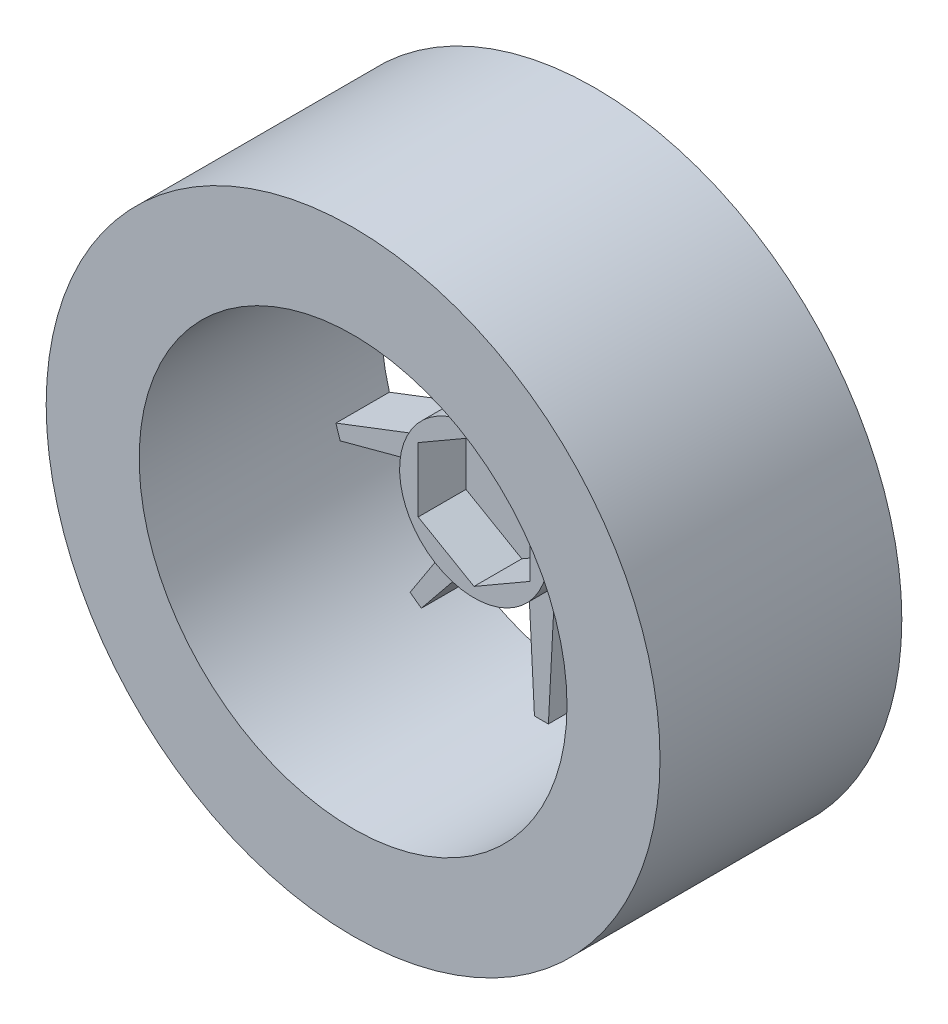
SolidWorks part; units mm, degrees
ref_plane "Front Plane" through (0, 0, 0) normal (0, 0, 1) x (1, 0, 0)
ref_plane "Top Plane" through (0, 0, 0) normal (0, 1, 0) x (1, 0, 0)
ref_plane "Right Plane" through (0, 0, 0) normal (1, 0, 0) x (0, 0, -1)
sketch "Sketch1" plane through (0, 0, 0) normal (0, 0, 1) x (1, 0, 0)
  circle A0 centre (0, 0) radius 33
  circle A1 centre (0, 0) radius 23
  dimension "D1" = 66
  dimension "D2" = 10
extrude "Boss-Extrude1" add sketch "Sketch1" along normal blind 26
sketch "Sketch3" plane through (0, 0, 0) normal (0, 0, 1) x (1, 0, 0)
  circle A0 centre (0, 0) radius 8
  circle A1 centre (0, 0) radius 1.875
  dimension "D1" = 16
  dimension "D2" = 3.75
extrude "Boss-Extrude2" add sketch "Sketch3" along normal blind 13 separate body
sketch "Sketch4" plane through (0, 0, 13) normal (0, 0, 1) x (1, 0, 0)
  line L0 (0, -14.3) -> (0, 14.3) construction
  line L1 (0, 6.9282) -> (-6, 3.4641)
  line L2 (-6, 3.4641) -> (-6, -3.4641)
  line L3 (-6, -3.4641) -> (0, -6.9282)
  line L4 (0, -6.9282) -> (6, -3.4641)
  line L5 (6, -3.4641) -> (6, 3.4641)
  line L6 (6, 3.4641) -> (0, 6.9282)
  circle A0 centre (0, 0) radius 6 construction
  point P1 (0, 6.5361)
  dimension "D1" = 12
extrude "Cut-Extrude1" cut sketch "Sketch4" against normal blind 5.14
sketch "Sketch5" plane through (0, 0, 0) normal (0, 0, 1) x (1, 0, 0)
  line L0 (-1.5, 8.5942) -> (-0.75, 22.9878)
  line L1 (0, -14.3) -> (0, 14.3) construction
  line L2 (1.5, 8.5942) -> (0.75, 22.9878)
  circle A0 centre (0, 0) radius 23 construction
  arc A1 (-1.5, 8.5942) -> (-2.221, 7.6855) centre (-2.4986, 8.6462) cw
  circle A2 centre (0, 0) radius 8 construction
  arc A3 (1.5, 8.5942) -> (2.221, 7.6855) centre (2.4986, 8.6462) ccw
  arc A4 (-0.75, 22.9878) -> (0.75, 22.9878) centre (0, 0) cw
  arc A5 (-2.221, 7.6855) -> (2.221, 7.6855) centre (0, 0) cw
  dimension "D3" = 1
  dimension "D1" = 0.75
  dimension "D2" = 1.5
extrude "Boss-Extrude3" add sketch "Sketch5" along normal blind 5.75 contours A1 A5 A3 L2 A4 L0 region at (0, 14.5735, 0)
ref_axis "Axis1" through (0, 0, 27.3) along (0, 0, -1)
pattern_circular "CirPattern1" count 10 over 360 about axis through (0, 0, 27.3) along (0, 0, -1) of "Boss-Extrude3"
